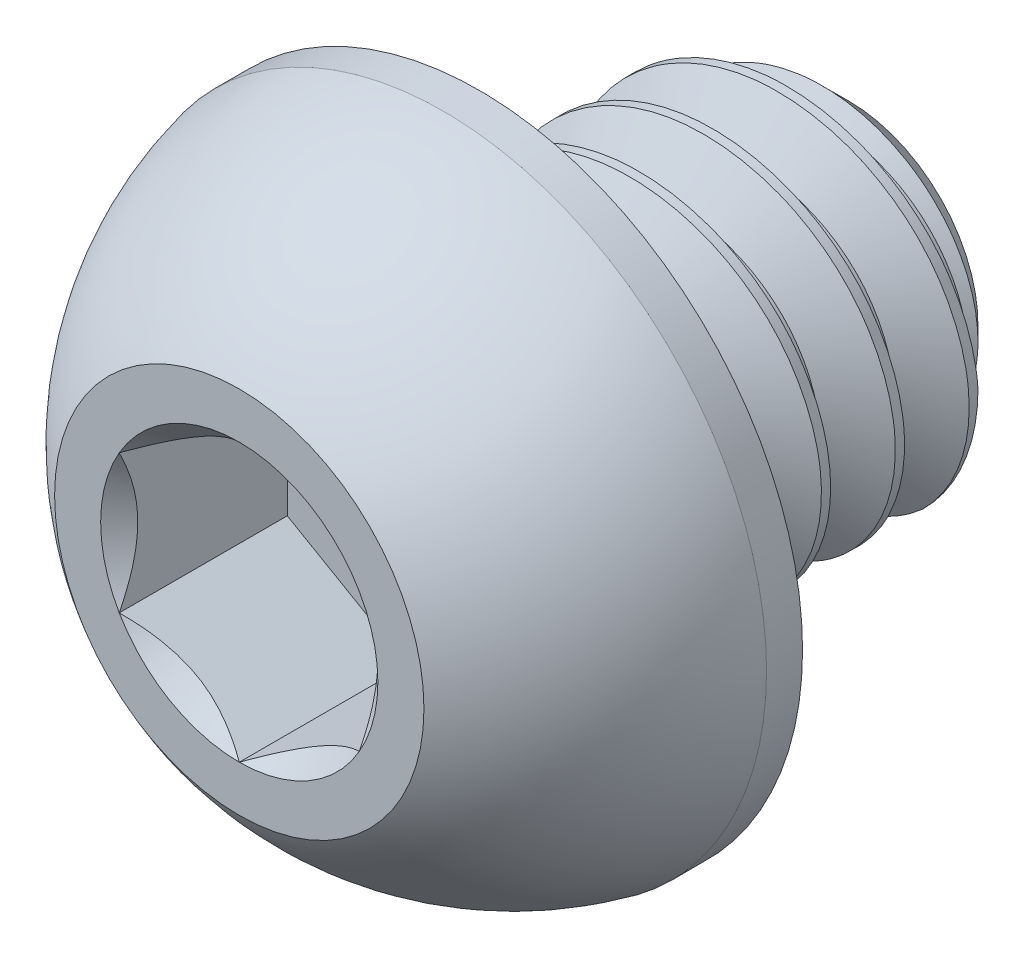
SolidWorks part; units mm, degrees
ref_plane "Front" through (0, 0, 0) normal (0, 0, 1) x (1, 0, 0)
ref_plane "Top" through (0, 0, 0) normal (0, 1, 0) x (1, 0, 0)
ref_plane "Right" through (0, 0, 0) normal (1, 0, 0) x (0, 0, -1)
sketch "Sketch1" plane through (0, 0, 0) normal (1, 0, 0) x (0, 0, -1)
  line L2 (1.3, 1) -> (3.3, 1)
  line L3 (3.3, 1) -> (3.3, 0)
  line L4 (3.3, 0) -> (1.3, 0)
  line L6 (1.105, 1.75) -> (1.3, 1.75) construction
  line L7 (3.3, 1) -> (3.3, -1) construction
  line L8 (0, 0) -> (1.3, 0) construction
  line L9 (1.3, 1.75) -> (1.3, -1.75) construction
  line L11 (1.3, 1) -> (1.3, 0)
  line L13 (0, 0.65) -> (0, -0.65) construction
  line L14 (0, 0.65) -> (0, 1) construction
  arc A3 (0, 1) -> (1.105, 1.75) centre (1.4858, 0) cw construction
  dimension "D1" = 0.195
revolve "Revolve1" add sketch "Sketch1" angle 360 mid plane about L4
sketch "Sketch3" plane through (0, 0, -3.3) normal (0, 0, -1) x (-1, 0, 0)
  circle A0 centre (0, 0) radius 1
curve "Helix/Spiral1" pitch 0.4 height 2.4 radius 1 centre (0, 0, -3.3) axis (0, 0, 1) start towards (0, 1, 0)
sketch "Sketch2" plane through (0, 0, 0) normal (1, 0, 0) x (0, 0, -1)
  line L0 (3.3, 1) -> (3.65, 1)
  line L1 (3.65, 1) -> (3.5, 0.7402)
  line L2 (3.5, 0.7402) -> (3.45, 0.7402)
  line L3 (3.45, 0.7402) -> (3.3, 1)
  line L4 (3.375, 0.8701) -> (3.575, 0.8701) construction
  dimension "D1" = 60
  dimension "D2" = 0.05
  dimension "D3" = 0.2
chamfer "Chamfer1" distance 0.3 angle 45 1 edges at (0, 1, -3.3)
sweep "Cut-Sweep1" cut profiles "Sketch2" path "Helix/Spiral1" align with end faces yes
sketch "Sketch7" plane through (0, 0, 0) normal (1, 0, 0) x (0, 0, -1)
  line L6 (1.105, 1.75) -> (1.3, 1.75) construction
  line L8 (0, 0) -> (1.3, 0) construction
  line L11 (1.3, 1.75) -> (1.3, -1.75) construction
  line L12 (1.105, 1.75) -> (1.3, 1.75)
  line L13 (0, 0) -> (1.3, 0)
  line L14 (0, 0.65) -> (0, -0.65) construction
  line L15 (1.3, 1.75) -> (1.3, 0)
  line L16 (0, 1) -> (0, 0)
  arc A2 (1.105, 1.75) -> (0, 1) centre (1.4858, 0) ccw construction
  arc A3 (1.105, 1.75) -> (0, 1) centre (1.4858, 0) ccw
revolve "Revolve2" add sketch "Sketch7" angle 360 mid plane about L13
sketch "Sketch5" plane through (0, 0, 0) normal (0, 0, 1) x (1, 0, 0)
  line L1 (0.65, -0.3753) -> (0.65, 0.3753)
  line L2 (0.65, 0.3753) -> (0, 0.7506)
  line L3 (0, 0.7506) -> (-0.65, 0.3753)
  line L4 (-0.65, 0.3753) -> (-0.65, -0.3753)
  line L5 (-0.65, -0.3753) -> (0, -0.7506)
  line L6 (0, -0.7506) -> (0.65, -0.3753)
  circle A0 centre (0, 0) radius 0.65 construction
extrude "Cut-Extrude2" cut sketch "Sketch5" against normal blind 0.91
sketch "Sketch6" plane through (0, 0, 0) normal (0, 0, 1) x (1, 0, 0)
  circle A0 centre (0, 0) radius 0.7506
extrude "Cut-Extrude3" cut sketch "Sketch6" against normal blind 0.91 draft 45
sketch "Sketch9" [suppressed] plane through (0, 0, -6.6) normal (0, 0, 1) x (1, 0, 0)
  circle A2 centre (0, 0) radius 6
extrude "Boss-Extrude2" [suppressed] add sketch "Sketch9" against normal offset from surface (19 mm away) 32 up to face at (0, 0.7, -3.3)
sketch "Sketch10" plane through (0, 0, 0) normal (1, 0, 0) x (0, 0, -1)
  line L0 (3.3, 1) -> (3.3, -1) construction
  point P0 (2.7, -1)
  dimension "D1" = 0.6
equation "\"D3@Helix/Spiral1\" = \"Lg@Sketch1\" + \"D4@Helix/Spiral1\""
equation "\"D2@Sketch2\" = \"D4@Helix/Spiral1\" * .125"
equation "\"D3@Sketch2\" = \"D4@Helix/Spiral1\" * .5"
equation "\"D1@Chamfer1\" = \"D4@Helix/Spiral1\" * .75"
equation "\"D1@Cut-Extrude2\" = \"Head Ht@Sketch1\" * .7"
equation "\"D1@Sketch1\" = \"Head Ht@Sketch1\" * .15"
equation "\"D1@Sketch10\" = \"D4@Helix/Spiral1\" * 1.5"
equation "\"D1@Cut-Extrude3\" = \"D1@Cut-Extrude2\""
